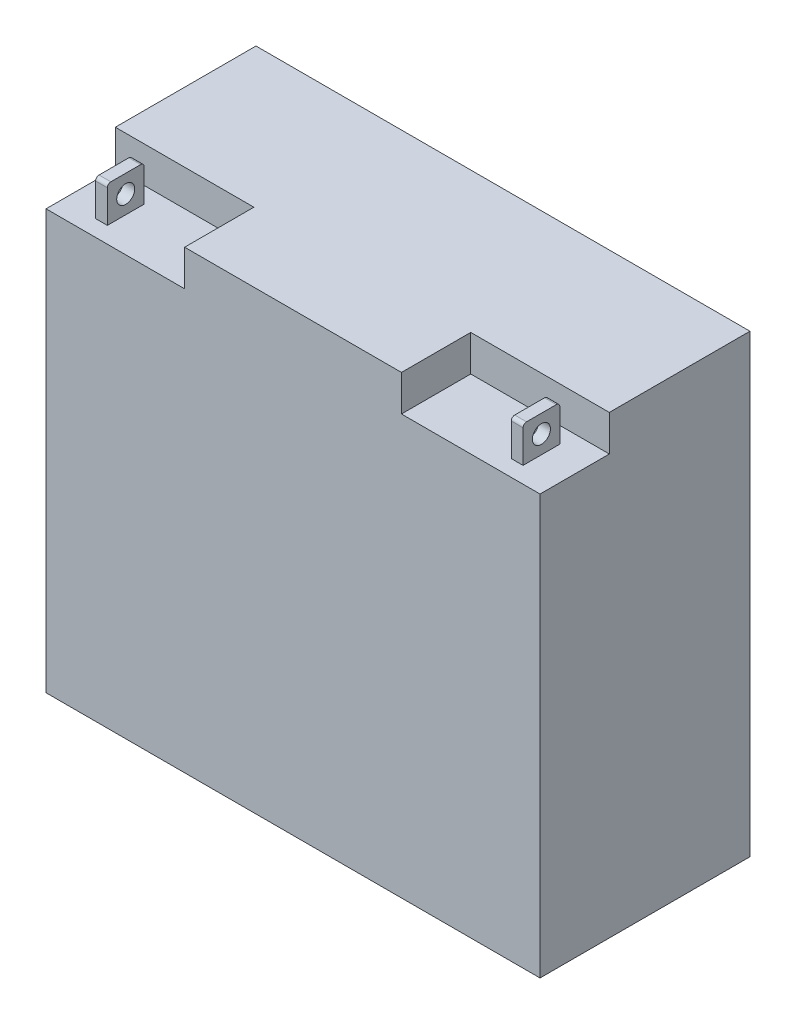
SolidWorks part; units mm, degrees
material "ABS"
ref_plane "Front Plane" through (0, 0, 0) normal (0, 0, 1) x (1, 0, 0)
ref_plane "Top Plane" through (0, 0, 0) normal (0, 1, 0) x (1, 0, 0)
ref_plane "Right Plane" through (0, 0, 0) normal (1, 0, 0) x (0, 0, -1)
sketch "Sketch2" plane through (0, 0, 0) normal (0, 1, 0) x (1, 0, 0)
  line L1 (-90.551, -38.481) -> (90.551, -38.481)
  line L2 (-90.551, -38.481) -> (-90.551, 38.481)
  line L3 (-90.551, 38.481) -> (90.551, 38.481)
  line L4 (90.551, -38.481) -> (90.551, 38.481)
  line L5 (-90.551, -38.481) -> (90.551, 38.481) construction
  line L6 (-90.551, 38.481) -> (90.551, -38.481) construction
  point P0 (0, 0)
  dimension "D1" = 181.102
  dimension "D2" = 76.962
extrude "Boss-Extrude1" add sketch "Sketch2" along normal blind 166.878
sketch "Sketch3" plane through (0, 166.878, 0) normal (0, 1, 0) x (1, 0, 0)
  line L0 (-88.7322, 0) -> (89.8475, 0) construction
  text T0 "Top" font "Century Gothic" height in points 36
wrap "Wrap1" [suppressed] sketch "Sketch3" source sketch "Sketch3" thickness 3.81 parameters "D1"=3.81
sketch "Sketch4" plane through (0, 166.878, 0) normal (0, 1, 0) x (1, 0, 0)
  line L0 (0, 0) -> (0, -38.481)
  line L1 (-90.551, -38.481) -> (90.551, -38.481) construction
  line L2 (0, 0) -> (0, 38.481)
  line L3 (90.551, 38.481) -> (-90.551, 38.481) construction
  line L4 (90.551, -13.081) -> (39.751, -13.081)
  line L5 (39.751, -13.081) -> (39.751, -38.481)
  line L8 (90.551, -38.481) -> (90.551, 38.481)
  line L9 (90.551, 38.481) -> (-90.551, 38.481)
  line L10 (-90.551, 38.481) -> (-90.551, -38.481)
  line L11 (-90.551, -38.481) -> (90.551, -38.481)
  line L12 (90.551, -38.481) -> (90.551, 38.481)
  line L13 (90.551, 38.481) -> (-90.551, 38.481)
  line L14 (-90.551, 38.481) -> (-90.551, -38.481)
  line L15 (-90.551, -38.481) -> (90.551, -38.481)
  line M7 (90.551, -38.481) -> (90.551, 38.481)
  line M8 (90.551, 38.481) -> (-90.551, 38.481)
  line M9 (-90.551, 38.481) -> (-90.551, -38.481)
  line M10 (-90.551, -38.481) -> (90.551, -38.481)
  dimension "D2" = 25.4
  dimension "D3" = 50.8
  dimension "D1" = 0
extrude "Cut-Extrude1" cut sketch "Sketch4" against normal through all contours L0 L2 M8 M9 M10 region at (-45.2755, 166.878, 0)
extrude "Cut-Extrude2" cut sketch "Sketch4<3>" against normal blind 13.208 contours L4 L5 M10 M7 region at (65.151, 166.878, 25.781)
sketch "Sketch4<3>" plane through (0, 166.878, 0) normal (0, 1, 0) x (1, 0, 0) same geometry as "Sketch4"
sketch "Sketch5" plane through (0, 153.67, 0) normal (0, 1, 0) x (1, 0, 0)
  line L0 (0, 38.481) -> (0, -38.481) construction
  line L1 (78.359, -32.512) -> (74.041, -32.512)
  line L2 (78.359, -32.512) -> (78.359, -19.05)
  line L3 (78.359, -19.05) -> (74.041, -19.05)
  line L4 (90.551, -13.081) -> (39.751, -13.081)
  line L5 (39.751, -13.081) -> (39.751, -38.481)
  line L6 (39.751, -38.481) -> (90.551, -38.481)
  line L7 (90.551, -38.481) -> (90.551, -13.081)
  line L8 (90.551, -13.081) -> (39.751, -13.081)
  line L9 (39.751, -13.081) -> (39.751, -38.481)
  line L10 (39.751, -38.481) -> (90.551, -38.481)
  line L11 (90.551, -38.481) -> (90.551, -13.081)
  line L12 (74.041, -32.512) -> (74.041, -19.05)
  line L13 (78.359, -32.512) -> (74.041, -19.05) construction
  line L14 (78.359, -19.05) -> (74.041, -32.512) construction
  line L15 (76.2, -25.781) -> (90.551, -25.781) construction
  point P2 (76.2, -25.781)
  dimension "D2" = 76.2
  dimension "D3" = 13.462
  dimension "D4" = 4.318
  dimension "D1" = 0
extrude "Boss-Extrude2" add sketch "Sketch5" along normal blind 13.208 contours L12 L1 L2 L3 region at (76.2, 153.67, 25.781)
sketch "Sketch6" plane through (78.359, 0, 0) normal (1, 0, 0) x (0, 0, -1)
  line L1 (-32.512, 153.67) -> (-25.781, 153.67)
  line L2 (-32.512, 153.67) -> (-32.512, 160.274)
  line L3 (-32.512, 160.274) -> (-25.781, 160.274) construction
  line L4 (-32.512, 153.67) -> (-19.05, 153.67)
  line L5 (-19.05, 153.67) -> (-19.05, 166.878)
  line L6 (-19.05, 166.878) -> (-32.512, 166.878)
  line L7 (-32.512, 166.878) -> (-32.512, 153.67)
  line L8 (-32.512, 153.67) -> (-19.05, 153.67)
  line L9 (-19.05, 153.67) -> (-19.05, 166.878)
  line L10 (-19.05, 166.878) -> (-32.512, 166.878)
  line L11 (-32.512, 166.878) -> (-32.512, 153.67)
  line L12 (-25.781, 153.67) -> (-25.781, 160.274) construction
  line L13 (-32.512, 166.878) -> (-32.512, 153.67) construction
  circle A0 centre (-25.781, 160.274) radius 3.302
  dimension "D2" = 6.604
  dimension "D1" = 0
extrude "Cut-Extrude3" cut sketch "Sketch6" against normal blind 13.208 contours A0 region at (78.359, 160.274, 25.781)
fillet "Fillet1" radius 1.27 2 edges at (76.2, 166.878, 19.05) (76.2, 166.878, 32.512)
mirror "Mirror1" about plane through (0, 0, 0) normal (-1, 0, 0) of bodies 105
